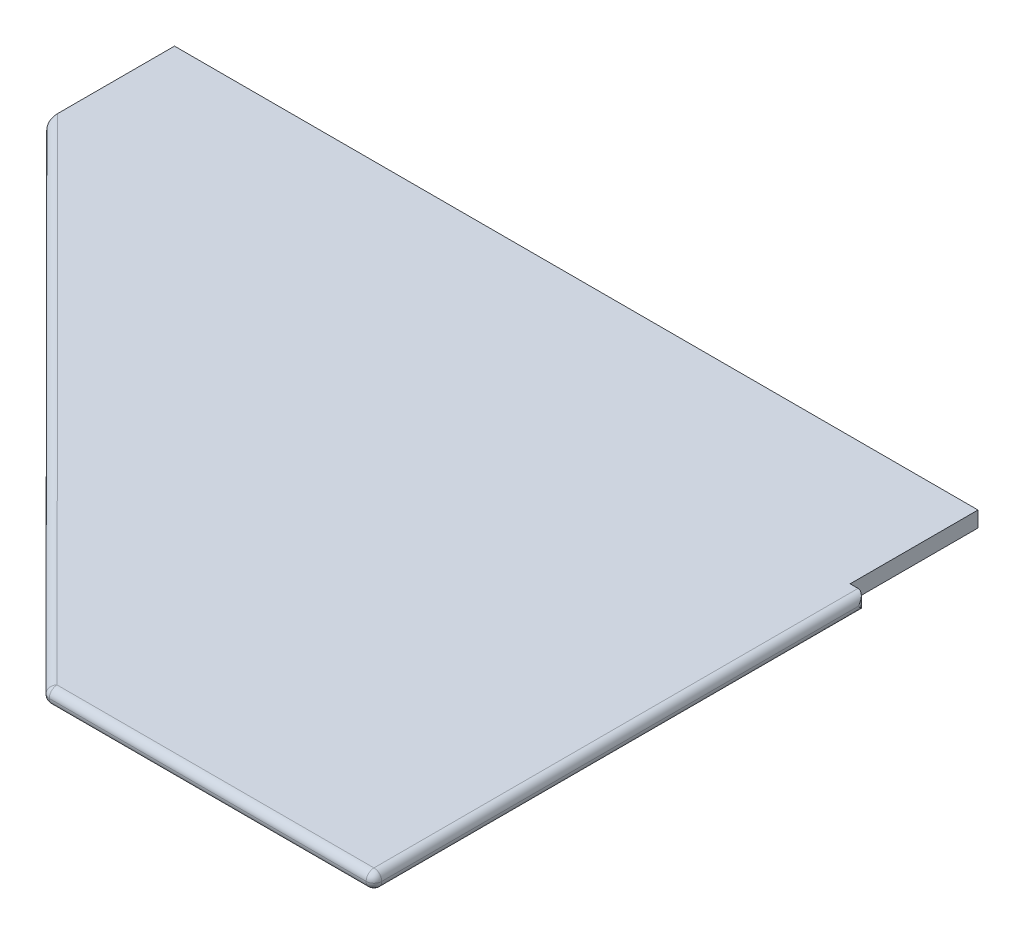
SolidWorks part; units mm, degrees
material "A-Glass Fiber"
ref_plane "Front Plane" through (0, 0, 0) normal (0, 0, 1) x (1, 0, 0)
ref_plane "Top Plane" through (0, 0, 0) normal (0, 1, 0) x (1, 0, 0)
ref_plane "Right Plane" through (0, 0, 0) normal (1, 0, 0) x (0, 0, -1)
sketch "Sketch1" plane through (0, 0, 0) normal (0, 1, 0) x (1, 0, 0)
  line L0 (0, 0) -> (0, 150)
  line L1 (0, 150) -> (-4.8006, 150)
  line L2 (-4.8006, 150) -> (-4.8006, 188.989)
  line L3 (-4.8006, 188.989) -> (-249.8006, 188.989)
  line L4 (-249.8006, 188.989) -> (-249.8006, 150)
  line L5 (-249.8006, 150) -> (-99.9998, 0)
  line L6 (-99.9998, 0) -> (0, 0)
  dimension "D1" = 245
  dimension "D2" = 38.989
  dimension "D3" = 99.9998
  dimension "D4" = 38.989
  dimension "D5" = 4.8006
  dimension "D6" = 150
extrude "Boss-Extrude2" add sketch "Sketch1" along normal blind 4.76
fillet "Fillet11" radius 2.38 10 edges at (-49.9999, 4.76, 0) (-49.9999, 0, 0) (0, 2.38, 0) (0, 4.76, -75) (0, 2.38, -150) (0, 0, -75) (-249.8006, 2.38, -150) (-174.9002, 4.76, -75) (-99.9998, 2.38, 0) (-174.9002, 0, -75)
